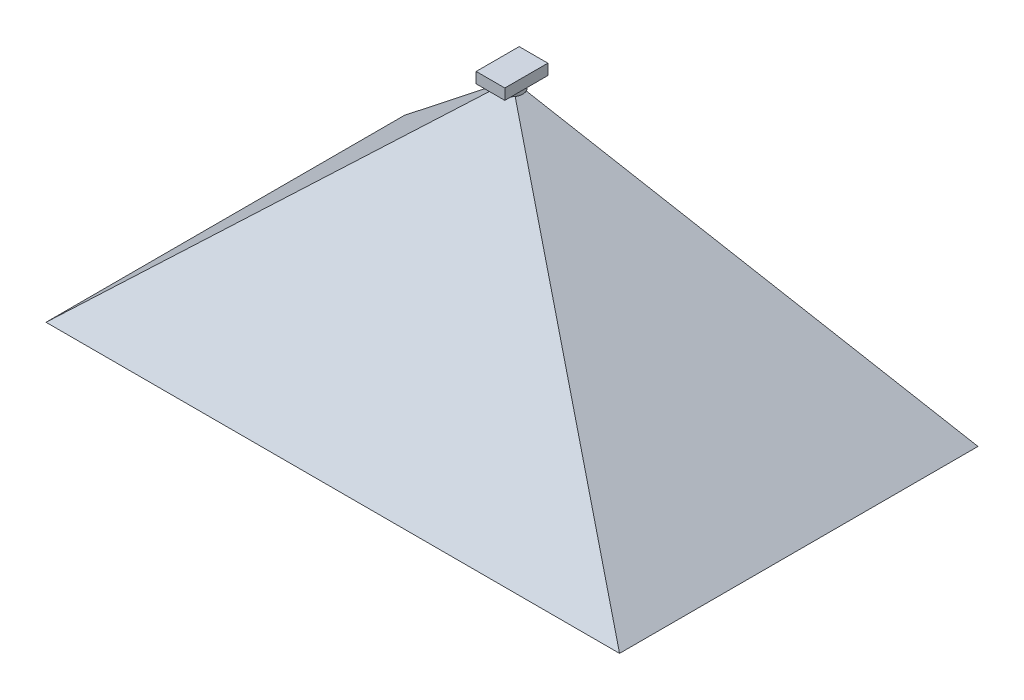
SolidWorks part; units mm, degrees
ref_plane "Front Plane" through (0, 0, 0) normal (0, 0, 1) x (1, 0, 0)
ref_plane "Top Plane" through (0, 0, 0) normal (0, 1, 0) x (1, 0, 0)
ref_plane "Right Plane" through (0, 0, 0) normal (1, 0, 0) x (0, 0, -1)
ref_plane "distance of measurement" through (0, 90.932, 0) normal (0, 1, 0) x (1, 0, 0)
sketch "Sketch1" plane through (0, 0, 0) normal (0, 1, 0) x (1, 0, 0)
  line L1 (-101.6, -63.5) -> (101.6, -63.5)
  line L2 (-101.6, -63.5) -> (-101.6, 63.5)
  line L3 (-101.6, 63.5) -> (101.6, 63.5)
  line L4 (101.6, -63.5) -> (101.6, 63.5)
  line L5 (-101.6, -63.5) -> (101.6, 63.5) construction
  line L6 (-101.6, 63.5) -> (101.6, -63.5) construction
  point P0 (0, 0)
sketch "Sketch2" plane through (0, 90.932, 0) normal (0, 1, 0) x (1, 0, 0)
  line L0 (-101.6, -63.5) -> (101.6, 63.5) construction
  line L1 (-2.7554, -1.7221) -> (2.7554, -1.7221)
  line L2 (-2.7554, -1.7221) -> (-2.7554, 1.7221)
  line L3 (-2.7554, 1.7221) -> (2.7554, 1.7221)
  line L4 (2.7554, -1.7221) -> (2.7554, 1.7221)
  line L5 (-2.7554, -1.7221) -> (2.7554, 1.7221) construction
  line L6 (-2.7554, 1.7221) -> (2.7554, -1.7221) construction
  point P0 (0, 0)
loft "FOV" add profiles "Sketch2", "Sketch1" connector at (-2.7554, 90.932, 1.7221) connector at (-101.6, 0, 63.5)
sketch "Sketch3" plane through (0, 90.932, 0) normal (0, 1, 0) x (1, 0, 0)
  circle A0 centre (0, 0) radius 3.81
extrude "camera lens" add sketch "Sketch3" along normal blind 2.54
sketch "Sketch4" plane through (0, 93.472, 0) normal (0, 1, 0) x (1, 0, 0)
  line L1 (5.08, -7.62) -> (-5.08, -7.62)
  line L2 (5.08, -7.62) -> (5.08, 7.62)
  line L3 (5.08, 7.62) -> (-5.08, 7.62)
  line L4 (-5.08, -7.62) -> (-5.08, 7.62)
  line L5 (5.08, -7.62) -> (-5.08, 7.62) construction
  line L6 (5.08, 7.62) -> (-5.08, -7.62) construction
  point P0 (0, 0)
extrude "camera holder" add sketch "Sketch4" along normal blind 3.81
ref_point "centre of vision"
